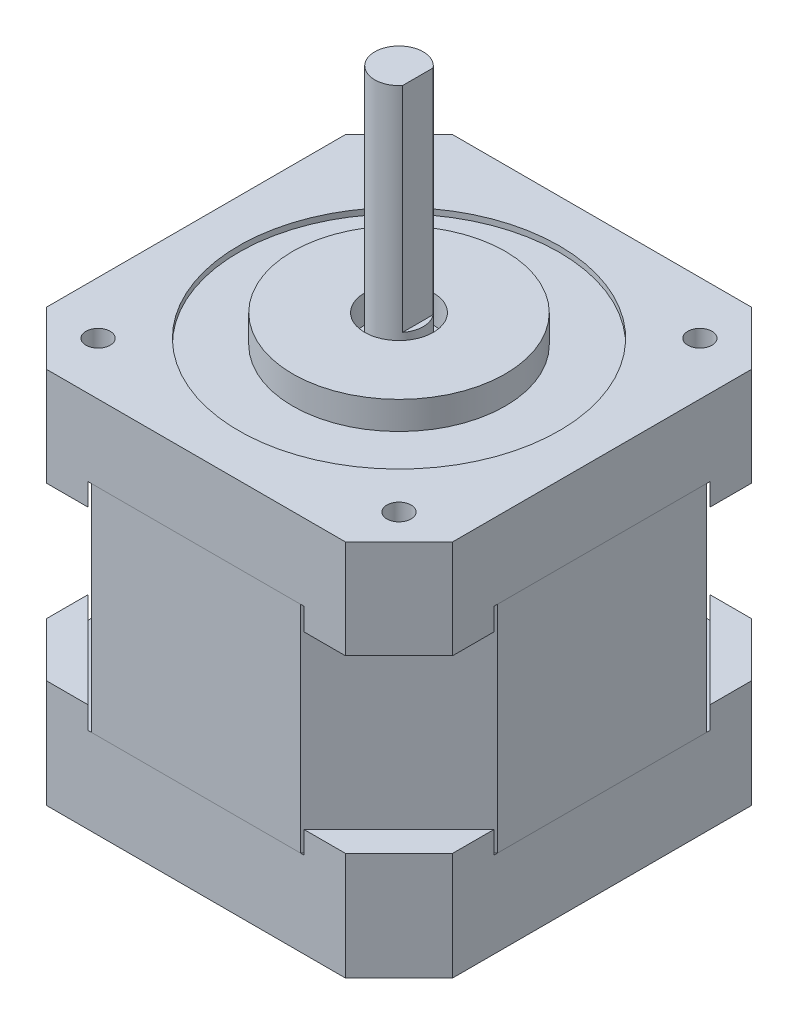
SolidWorks part; units mm, degrees
material "Plain Carbon Steel"
ref_plane "Front Plane" through (0, 0, 0) normal (0, 0, 1) x (1, 0, 0)
ref_plane "Top Plane" through (0, 0, 0) normal (0, 1, 0) x (1, 0, 0)
ref_plane "Right Plane" through (0, 0, 0) normal (1, 0, 0) x (0, 0, -1)
sketch "Sketch2" plane through (0, 0, 0) normal (0, 0, 1) x (1, 0, 0)
  line L0 (0, 0) -> (0, 63.2206)
  line L1 (0, 63.2206) -> (2.5, 63.2206)
  line L2 (2.5, 63.2206) -> (2.5, 38.3286)
  line L3 (2.5, 38.3286) -> (3.5306, 38.3286)
  line L4 (3.5306, 38.3286) -> (3.5306, 41.1988)
  line L5 (3.5306, 41.1988) -> (10.9474, 41.1988)
  line L6 (10.9474, 41.1988) -> (10.9474, 38.3286)
  line L7 (10.9474, 38.3286) -> (16.51, 38.3286)
  line L8 (16.51, 38.3286) -> (16.51, 38.9128)
  line L9 (16.51, 38.9128) -> (20.9296, 38.9128)
  line L10 (20.9296, 38.9128) -> (20.9296, 0)
  line L11 (20.9296, 0) -> (0, 0)
  dimension "D1" = 2.5
  dimension "D2" = 16.51
  dimension "D3" = 10.9474
  dimension "D4" = 20.9296
  dimension "D5" = 38.9128
  dimension "D6" = 22.0218
  dimension "D7" = 2.8702
  dimension "D8" = 0.5842
  dimension "D9" = 3.5306
revolve "Revolve1" add sketch "Sketch2" angle 360 about L0
sketch "Sketch3" plane through (0, 63.2206, 0) normal (0, 1, 0) x (1, 0, 0)
  line L0 (-2.5, 0) -> (-2.5, 5.6816) construction
  line L1 (1.945, 5.9414) -> (8.3861, 5.9414)
  line L2 (1.945, 5.9414) -> (1.945, -3.6648)
  line L3 (1.945, -3.6648) -> (8.3861, -3.6648)
  line L4 (8.3861, 5.9414) -> (8.3861, -3.6648)
  circle A0 centre (0, 0) radius 2.5 construction
  circle A1 centre (0, 0) radius 2.5 construction
  dimension "D1" = 4.445
extrude "Cut-Extrude1" cut sketch "Sketch3" against normal up to surface (22.0218 mm away) up to face at (0, 41.1988, -3.5306)
sketch "Sketch4" plane through (0, 0, 0) normal (0, 1, 0) x (1, 0, 0)
  line L1 (-20.9296, 20.9296) -> (20.9296, 20.9296)
  line L2 (-20.9296, 20.9296) -> (-20.9296, -20.9296)
  line L3 (-20.9296, -20.9296) -> (20.9296, -20.9296)
  line L4 (20.9296, 20.9296) -> (20.9296, -20.9296)
  circle A0 centre (0, 0) radius 20.9296 construction
  circle A1 centre (0, 0) radius 20.9296 construction
  circle A2 centre (0, 0) radius 18.3896
  dimension "D1" = 2.54
extrude "Boss-Extrude1" add sketch "Sketch4" along normal up to surface (38.9128 mm away) contours L4 L1 L2 L3 A2 region at (0, 0, -20.3376) up to face at (0, 38.9128, -16.51)
ref_axis "Axis2" through (0, -3.161, 0) along (0, 1, 0)
ref_plane "Plane1" through (0, 0, 0) normal (0.7071, 0, 0.7071) x (0, 1, 0)
sketch "Sketch5" plane through (0, 0, 0) normal (0.7071, 0, 0.7071) x (0, 1, 0)
  line L0 (0, 25.6873) -> (11.1252, 25.6873)
  line L2 (11.1252, 25.6873) -> (11.1252, 22.4107) construction
  line L3 (11.1252, 22.4107) -> (28.7528, 22.4107)
  line L4 (28.7528, 22.4107) -> (28.7528, 25.6873) construction
  line L5 (28.7528, 25.6873) -> (38.9128, 25.6873)
  line L6 (0, 29.5989) -> (0, 0) construction
  line L7 (38.9128, 29.5989) -> (0, 29.5989) construction
  line L8 (38.9128, 29.5989) -> (38.9128, 0) construction
  line L9 (0, 25.6873) -> (-11.3932, 25.6873)
  line L10 (-11.3932, 25.6873) -> (-11.3932, 38.3996)
  line L11 (-11.3932, 38.3996) -> (48.4361, 38.3996)
  line L12 (48.4361, 38.3996) -> (48.4361, 25.6873)
  line L13 (48.4361, 25.6873) -> (38.9128, 25.6873)
  line L14 (11.1252, 25.6873) -> (11.1252, 22.6647)
  line L15 (11.1252, 22.6647) -> (8.8392, 22.6647)
  line L16 (8.8392, 22.6647) -> (8.8392, 22.4107)
  line L17 (8.8392, 22.4107) -> (11.1252, 22.4107)
  line L18 (28.7528, 25.6873) -> (28.7528, 22.6647)
  line L19 (28.7528, 22.6647) -> (31.0388, 22.6647)
  line L20 (31.0388, 22.6647) -> (31.0388, 22.4107)
  line L21 (31.0388, 22.4107) -> (28.7528, 22.4107)
  dimension "D1" = 10.16
  dimension "D2" = 11.1252
  dimension "D3" = 7.1882
  dimension "D4" = 3.9116
  dimension "D5" = 2.286
  dimension "D6" = 2.286
  dimension "D7" = 0.254
  dimension "D8" = 0.254
extrude "Cut-Extrude2" cut sketch "Sketch5" against normal through all and the other way through all
pattern_circular "CirPattern1" count 4 over 360 about axis through (0, -3.161, 0) along (0, 1, 0) of "Cut-Extrude2"
sketch "Sketch8" plane through (0, 0, 0) normal (0, 0, 1) x (1, 0, 0)
  line L0 (10.764, 8.8392) -> (10.764, 31.0388) construction
  line L1 (-10.764, 31.0388) -> (-10.764, 8.8392) construction
  line L2 (10.764, 8.8392) -> (10.764, 31.0388) construction
  line L3 (-10.764, 31.0388) -> (-10.764, 8.8392) construction
  line L4 (-10.764, 31.0388) -> (10.764, 31.0388)
  line L5 (10.764, 8.8392) -> (-10.764, 8.8392)
split line "Split Line2"
sketch "Sketch9" plane through (0, 0, 0) normal (1, 0, 0) x (0, 0, -1)
  line L0 (10.764, 31.0388) -> (10.764, 8.8392) construction
  line L1 (-10.764, 8.8392) -> (-10.764, 31.0388) construction
  line L2 (10.764, 31.0388) -> (10.764, 8.8392) construction
  line L3 (-10.764, 8.8392) -> (-10.764, 31.0388) construction
  line L4 (-10.764, 31.0388) -> (10.764, 31.0388)
  line L5 (10.764, 8.8392) -> (-10.764, 8.8392)
split line "Split Line3"
sketch "Sketch10" plane through (0, 38.9128, 0) normal (0, 1, 0) x (1, 0, 0)
  line L0 (-15.5, 15.5) -> (0, 0) construction
  line L1 (0, 0) -> (-32.797, 0) construction
  circle A0 centre (-15.5, 15.5) radius 1.25
  circle A1 centre (15.5, 15.5) radius 1.25
  circle A2 centre (15.5, -15.5) radius 1.25
  circle A3 centre (-15.5, -15.5) radius 1.25
  point P14 (0, 0)
  dimension "D2" = 2.5
  dimension "D1" = 45
  dimension "D3" = 15.5
  dimension "D4" = 4
extrude "Cut-Extrude3" cut sketch "Sketch10" against normal blind 4
